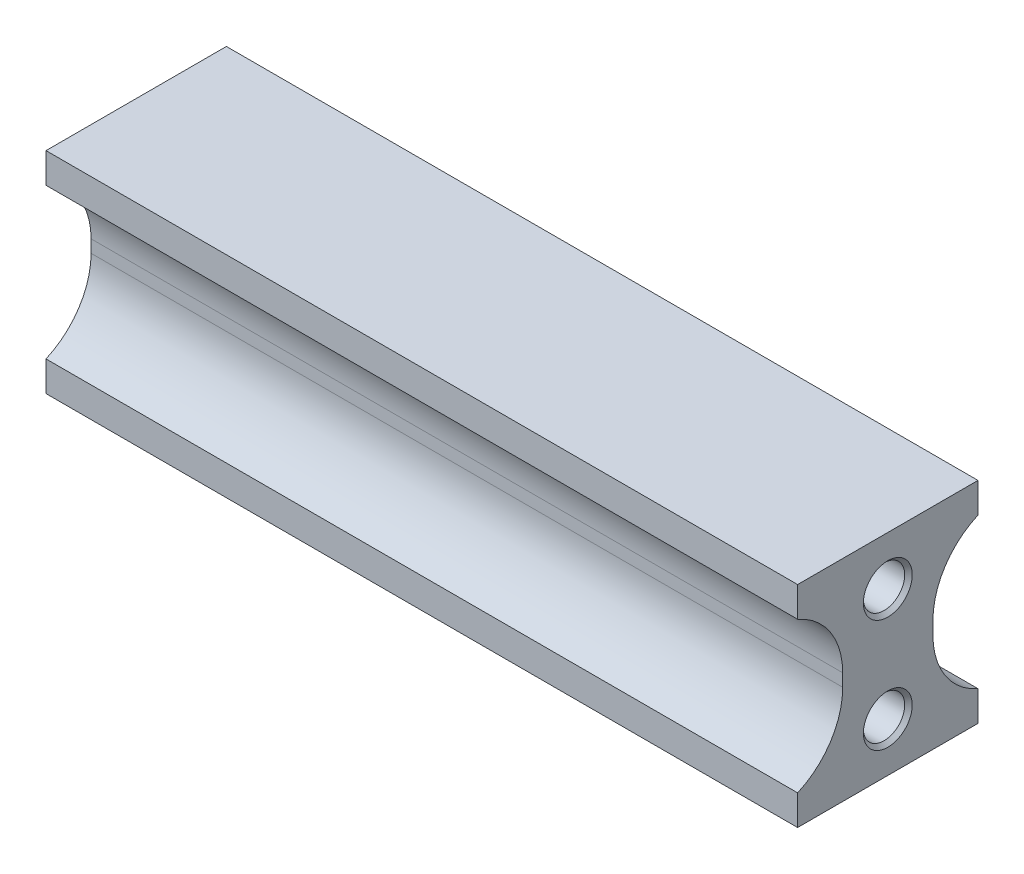
SolidWorks part; units mm, degrees
ref_plane "前视基准面" through (0, 0, 0) normal (0, 0, 1) x (1, 0, 0)
ref_plane "上视基准面" through (0, 0, 0) normal (0, 1, 0) x (1, 0, 0)
ref_plane "右视基准面" through (0, 0, 0) normal (1, 0, 0) x (0, 0, -1)
sketch "草图1" plane through (0, 0, 0) normal (1, 0, 0) x (0, 0, -1)
  line L0 (-12, 0) -> (12, 0)
  line L1 (12, 0) -> (12, 4)
  line L2 (12, 4) -> (6, 4)
  line L3 (6, 4) -> (6, 24)
  line L4 (6, 24) -> (12, 24)
  line L5 (12, 24) -> (12, 28)
  line L6 (12, 28) -> (-12, 28)
  line L7 (0, 27.5067) -> (0, 40132.5483) construction
  line L8 (-12, 24) -> (-12, 28)
  line L9 (-6, 24) -> (-12, 24)
  line L10 (-6, 4) -> (-6, 24)
  line L11 (-12, 4) -> (-6, 4)
  line L12 (-12, 0) -> (-12, 4)
  circle A0 centre (0, 21.5) radius 2.75
  circle A1 centre (0, 6.5) radius 2.75
  point P12 (0, 28)
  point P17 (0, 0)
  point P21 (-6, 14)
  dimension "D7" = 5.5
  dimension "D1" = 12
  dimension "D2" = 12
  dimension "D3" = 20
  dimension "D4" = 4
  dimension "D5" = 4
  dimension "D6" = 6
  dimension "D8" = 15
  dimension "D9" = 7.5
extrude "凸台-拉伸1" add sketch "草图1" along normal blind 100
fillet "圆角1" radius 10 4 edges at (50, 24, -6) (50, 4, -6) (50, 4, 6) (50, 24, 6)
chamfer "倒角1" distance 0.5 angle 45 4 edges at (0, 6.5, -2.75) (100, 6.5, -2.75) (0, 21.5, -2.75) (100, 21.5, -2.75)
